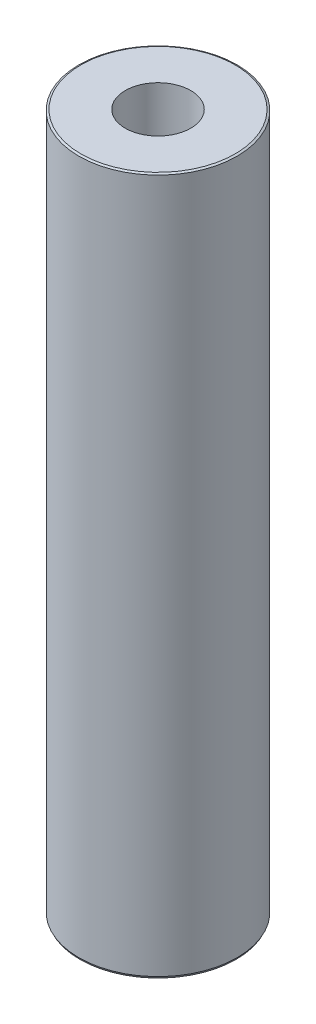
SolidWorks part; units mm, degrees
ref_plane "Front Plane" through (0, 0, 0) normal (0, 0, 1) x (1, 0, 0)
ref_plane "Top Plane" through (0, 0, 0) normal (0, 1, 0) x (1, 0, 0)
ref_plane "Right Plane" through (0, 0, 0) normal (1, 0, 0) x (0, 0, -1)
sketch "Sketch1" plane through (0, 0, 0) normal (0, 1, 0) x (1, 0, 0)
  circle A0 centre (0, 0) radius 45
  dimension "SHAFT_OD" = 90
extrude "Boss-Extrude1" add sketch "Sketch1" along normal blind 396.3607
sketch "Sketch2" plane through (0, 0, 0) normal (0, 1, 0) x (1, 0, 0)
  circle A0 centre (0, 0) radius 18.6029
  dimension "BORE_D" = 37.2058
extrude "Cut-Extrude1" cut sketch "Sketch2" along normal through all
chamfer "Chamfer1" distance 0.5536 angle 63.986 2 edges at (0, 396.3607, 45) (0, 0, 45) first distance on face at (0, 396.3607, 45) first distance on face at (0, 0, 18.6029)
